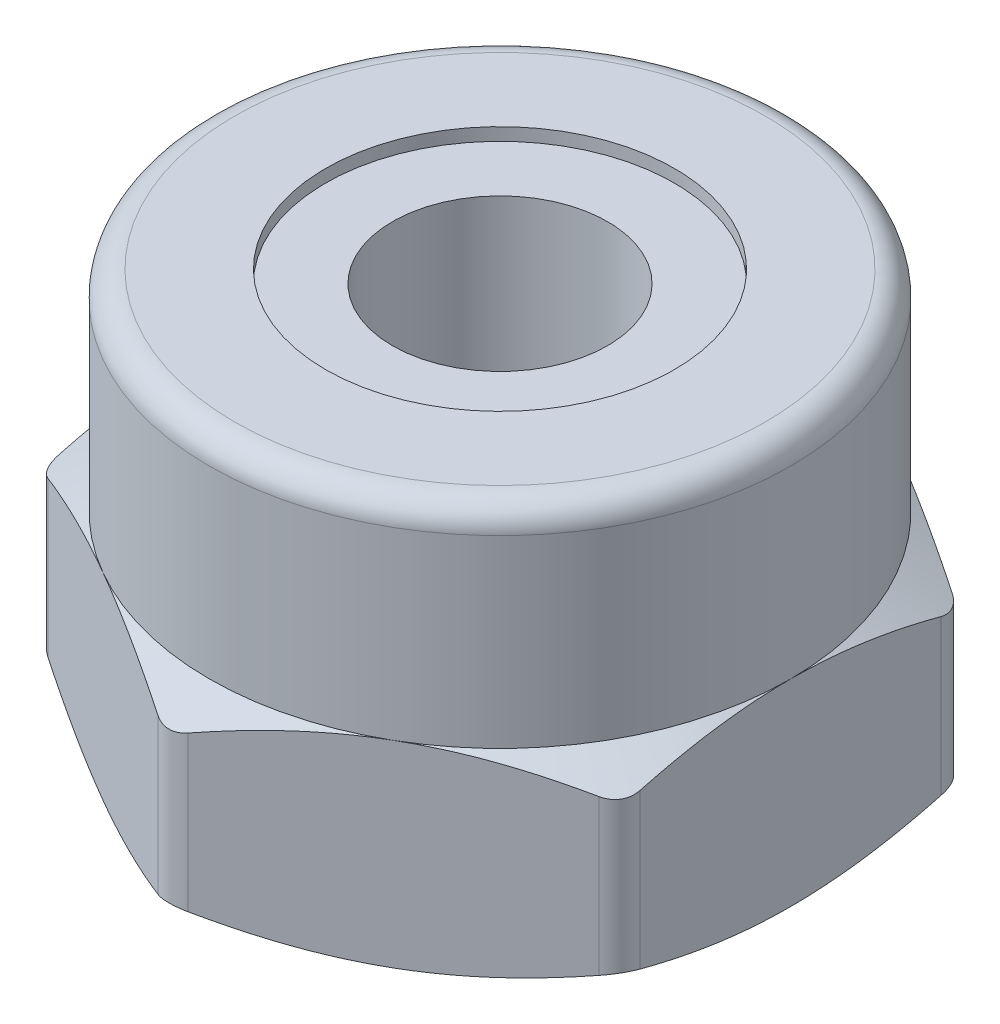
SolidWorks part; units mm, degrees
ref_plane "Front Plane" through (0, 0, 0) normal (0, 0, 1) x (1, 0, 0)
ref_plane "Top Plane" through (0, 0, 0) normal (0, 1, 0) x (1, 0, 0)
ref_plane "Right Plane" through (0, 0, 0) normal (1, 0, 0) x (0, 0, -1)
sketch "Sketch1" plane through (0, 0, 0) normal (0, 0, 1) x (1, 0, 0)
  line L0 (-2, -1.4) -> (2, -1.4) construction
  line L1 (-2, -1.4) -> (-2, -0.0433) construction
  line L2 (-2, -0.0433) -> (2, -0.0433) construction
  line L7 (2, -0.0433) -> (2, -1.4) construction
  line L8 (0, 1.4) -> (0, -1.4) construction
  line L9 (-1, 1.4) -> (-1, -1.4) construction
  line L10 (1, 1.4) -> (1, -1.4) construction
  line L11 (-1, 1.4) -> (1, 1.4) construction
  line L14 (2, -1.4) -> (2.3089, -1.2217) construction
  line L15 (2, -0.0433) -> (2, 1.4) construction
  line L16 (2, 1.4) -> (1, 1.4) construction
  line L17 (2.3089, -1.2217) -> (2.3089, -0.2217) construction
  line L18 (-2, -0.0433) -> (-2, 1.4) construction
  line L19 (-2, 1.4) -> (-1, 1.4) construction
  line L20 (2.3089, -0.2217) -> (2, -0.0433) construction
  line L21 (-1, -1.4) -> (-1, -1.75) construction
  line L22 (-1, -1.75) -> (-0.6969, -1.575) construction
  line L23 (-0.6969, -1.575) -> (-1, -1.4) construction
  line L24 (-1.0433, -1.375) -> (-1.0433, -1.775) construction
  line L25 (-1.0433, -1.375) -> (-1, -1.4) construction
  line L26 (-1, -1.75) -> (-1.0433, -1.775) construction
  line L27 (-0.7402, -1.55) -> (-0.7402, -1.6) construction
  line L28 (-1, -1.575) -> (-1.0433, -1.575) construction
  line L29 (-0.7402, -1.575) -> (-0.6969, -1.575) construction
  dimension "Width | s" = 4
  dimension "Thread Diameter" = 2
  dimension "Height | h" = 2.8
  dimension "D1" = 4.6178
  dimension "D2" = 30
  dimension "Flats Height" = 1
  dimension "Thread Pitch" = 0.4
  dimension "D4" = 0.05
sketch "Sketch2" plane through (0, 0, 0) normal (0, 1, 0) x (1, 0, 0)
  line L0 (0, 0) -> (1, 1.7321) construction
  line L1 (2, 1.1547) -> (0, 2.3094)
  line L2 (0, 2.3094) -> (-2, 1.1547)
  line L3 (-2, 1.1547) -> (-2, -1.1547)
  line L4 (-2, -1.1547) -> (0, -2.3094)
  line L5 (0, -2.3094) -> (2, -1.1547)
  line L6 (2, -1.1547) -> (2, 1.1547)
  line L7 (0, 0) -> (2, 1.1547) construction
  circle A0 centre (0, 0) radius 2 construction
  circle A1 centre (0, 0) radius 2.3094 construction
extrude "Boss-Extrude1" add sketch "Sketch2" against normal up to vertex (1.4 mm away) from vertex up to point (2, -1.4, 0) starting at point (2, -0.0433, 0)
sketch "Sketch3" plane through (0, 0, 0) normal (0, 0, 1) x (1, 0, 0)
  line L3 (1, 0.534) -> (2.3189, -0.2274)
  line L4 (1, 1.4) -> (1, -1.4) construction
  line L5 (1, -1.9774) -> (2.3189, -1.2159)
  line L6 (2.3189, -1.2159) -> (2.3189, -1.9774)
  line L7 (2.3189, -1.9774) -> (1, -1.9774)
  line L8 (1, 0.534) -> (2.3189, 0.534)
  line L10 (2.3189, -0.2274) -> (2.3189, 0.534)
  dimension "D1" = 0.01
revolve "Cut-Revolve1" cut sketch "Sketch3" angle 360 about L8
fillet "Fillet1" radius 0.2059 6 edges at (-2, -0.7217, -1.1547) (-2, -0.7217, 1.1547) (0, -0.7217, 2.3094) (0, -0.7217, -2.3094) (2, -0.7217, -1.1547) (2, -0.7217, 1.1547)
sketch "Sketch5" plane through (0, 0, 0) normal (0, 0, 1) x (1, 0, 0)
  line L0 (-1.2, -1.4) -> (-1, -1.2)
  line L1 (-2, -1.4) -> (2, -1.4) construction
  line L2 (-1, 1.4) -> (-1, -1.4) construction
  line L3 (-1, -1.2) -> (-1, -0.2433)
  line L4 (-1, -0.2433) -> (-1.2, -0.0433)
  line L5 (-2, -0.0433) -> (2, -0.0433) construction
  line L6 (-1.2, -0.0433) -> (0, -0.0433)
  line L7 (0, -0.0433) -> (0, -1.4)
  line L8 (0, -1.4) -> (-1.2, -1.4)
  line L9 (0, 1.4) -> (0, -1.4) construction
  dimension "D1" = 45
  dimension "D2" = 0.2
revolve "Cut-Revolve2" cut sketch "Sketch5" angle 360 about L8
sketch "Sketch4" plane through (0, 0, 0) normal (0, 0, 1) x (1, 0, 0)
  line L0 (-1.2, 1.4) -> (-1.825, 1.4)
  line L1 (-2, 1.4) -> (-1, 1.4) construction
  line L2 (-2, 1.225) -> (-2, -0.0433)
  line L4 (-1.825, 1.4) -> (-1.825, 1.225) construction
  line L5 (-0.8484, -1.4875) -> (-0.8484, -1.6625) construction
  line L6 (-0.6969, -1.575) -> (-1, -1.4) construction
  line L7 (-1, -1.75) -> (-0.6969, -1.575) construction
  line L8 (-2, -0.0433) -> (-1.9125, -0.0433)
  line L10 (-1.2, 1.3125) -> (-1.2, 1.4)
  line L11 (-1.2, 1.3125) -> (-1.825, 1.3125)
  line L12 (-1.9125, 1.225) -> (-1.9125, -0.0433)
  arc A0 (-2, 1.225) -> (-1.825, 1.4) centre (-1.825, 1.225) cw
  arc A1 (-1.825, 1.3125) -> (-1.9125, 1.225) centre (-1.825, 1.225) ccw
revolve "Revolve1" add sketch "Sketch4" angle 360 about L8
sketch "Sketch6" plane through (0, 0, 0) normal (0, 0, 1) x (1, 0, 0)
  line L0 (-2, -0.0433) -> (2, -0.0433) construction
  line L1 (-1.825, 1.3125) -> (-0.7402, 1.3125)
  line L2 (-1.9125, 1.225) -> (-1.9125, -0.0433)
  line L3 (-1.9125, -0.0433) -> (-0.7402, -0.0433)
  line L4 (-0.7402, 1.3125) -> (-0.7402, -0.0433)
  arc A0 (-1.825, 1.3125) -> (-1.9125, 1.225) centre (-1.825, 1.225) ccw
revolve "Revolve2" add sketch "Sketch6" angle 360 about L8
sketch "Sketch7" plane through (0, -1.4, 0) normal (0, 1, 0) x (-1, 0, 0)
  line L0 (1, 0) -> (-1, 0) construction
  line L1 (0, 0) -> (-0.7071, -0.7071) construction
  circle A0 centre (0, 0) radius 1
  point P7 (-0.7071, -0.7071)
  dimension "D1" = 225
curve "Helix/Spiral1" pitch 0.4 height 2.8 radius 1 left hand yes centre (0, -1.4, 0) axis (0, 1, 0) start towards (0, 0, 1)
sketch "Sketch8" plane through (0, 0, 0) normal (0, 0, 1) x (1, 0, 0)
  line L0 (-1.0217, -1.3875) -> (-1.0217, -1.7625)
  line L1 (-1.0433, -1.375) -> (-1, -1.4) construction
  line L2 (-1, -1.75) -> (-1.0433, -1.775) construction
  line L3 (-1.0217, -1.7625) -> (-0.7402, -1.6)
  line L4 (-0.7402, -1.6) -> (-0.7402, -1.55)
  line L5 (-0.7402, -1.55) -> (-1.0217, -1.3875)
sweep "Sweep1" add profiles "Sketch8" path "Helix/Spiral1"
sketch "Sketch9" plane through (0, 0, 0) normal (0, 0, 1) x (1, 0, 0)
  line L0 (-1.2, 1.4875) -> (-1.2, -0.0433)
  line L1 (-1.2, -0.0433) -> (-0.6969, -0.5464)
  line L2 (-0.6969, -0.5464) -> (-0.6969, 1.4875)
  line L4 (-0.6969, 1.4875) -> (-1.2, 1.4875)
  line L5 (-0.6969, -0.8969) -> (-1.2, -1.4)
  line L6 (-1.2, -1.4) -> (-1.2, -1.775)
  line L7 (-1.2, -1.775) -> (-0.6969, -1.775)
  line L8 (-0.6969, -1.775) -> (-0.6969, -0.8969)
  line L9 (-0.9484, 1.4875) -> (-0.9484, 1.4) construction
  line L10 (-1, 1.4) -> (1, 1.4) construction
  line L12 (-1.2, 1.3125) -> (-1.2, 1.4) construction
revolve "Cut-Revolve3" cut sketch "Sketch9" angle 360 about L8
equation "\"D1@Sketch1\"=\"Width | s@Sketch1\"*(1.15+.04/9)"
equation "\"D1@Fillet1\"=(\"D1@Sketch1\"-\"Width | s@Sketch1\")/3"
equation "\"D4@Sketch1\" = \"Thread Pitch@Sketch1\" / 8"
equation "\"D2@Sketch5\"=\"Thread Pitch@Sketch1\"*.5"
equation "\"D3@Helix/Spiral1\"=\"Height | h@Sketch1\""
equation "\"D4@Helix/Spiral1\"=\"Thread Pitch@Sketch1\""
